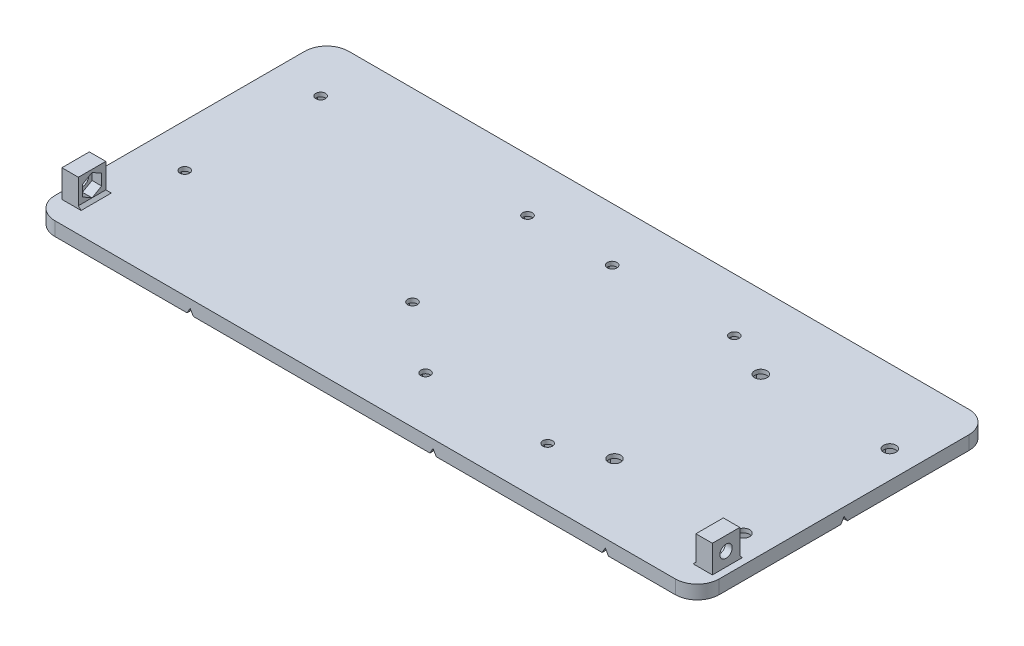
SolidWorks part; units mm, degrees
ref_plane "Front Plane" through (0, 0, 0) normal (0, 0, 1) x (1, 0, 0)
ref_plane "Top Plane" through (0, 0, 0) normal (0, 1, 0) x (1, 0, 0)
ref_plane "Right Plane" through (0, 0, 0) normal (1, 0, 0) x (0, 0, -1)
sketch "Sketch3" plane through (0, 0, 0) normal (0, 1, 0) x (1, 0, 0)
  line L0 (-65.75, 19.405) -> (13.75, 19.405) construction
  line L1 (-67.5, 17.655) -> (-67.5, 16.655) construction
  line L2 (20.25, 16.655) -> (-82.25, 16.655) construction
  line L3 (82.25, -3.845) -> (32.25, -3.845) construction
  line L4 (20.25, 16.655) -> (20.25, 69.655) construction
  line L5 (20.25, 69.655) -> (-82.25, 69.655) construction
  line L6 (-82.25, 16.655) -> (-82.25, 69.655) construction
  line L7 (-69.25, 19.405) -> (-82.25, 19.405) construction
  line L8 (17.25, 19.405) -> (20.25, 19.405) construction
  line L9 (15.5, 17.655) -> (15.5, 16.655) construction
  line L10 (-82.25, 69.655) -> (-82.25, 75.655) construction
  line L11 (-82.25, 69.655) -> (-88.25, 69.655) construction
  line L12 (-79.25, 6.345) -> (-79.25, 7.345) construction
  line L13 (-81.25, 7.345) -> (-15.25, 7.345) construction
  line L14 (-81.25, 7.345) -> (-81.25, -68.655) construction
  line L15 (-81.25, -68.655) -> (-15.25, -68.655) construction
  line L16 (-15.25, 7.345) -> (-15.25, -68.655) construction
  line L17 (-80.25, 5.345) -> (-81.25, 5.345) construction
  line L18 (-17.25, 6.345) -> (-17.25, 7.345) construction
  line L19 (-16.25, 5.345) -> (-15.25, 5.345) construction
  line L20 (-16.25, -66.655) -> (-15.25, -66.655) construction
  line L21 (-17.25, -67.655) -> (-17.25, -68.655) construction
  line L22 (-80.25, -66.655) -> (-81.25, -66.655) construction
  line L23 (-79.25, -67.655) -> (-79.25, -68.655) construction
  line L24 (82.25, -3.845) -> (82.25, 69.655) construction
  line L25 (82.25, 69.655) -> (32.25, 69.655) construction
  line L26 (32.25, -3.845) -> (32.25, 69.655) construction
  line L27 (26.74, -7.845) -> (82.25, -7.845) construction
  line L28 (26.74, -7.845) -> (26.74, -69.655) construction
  line L29 (26.74, -69.655) -> (82.25, -69.655) construction
  line L30 (82.25, -7.845) -> (82.25, -69.655) construction
  line L31 (-88.25, 75.655) -> (88.25, 75.655) construction
  line L32 (-88.25, 75.655) -> (-88.25, -75.655) construction
  line L33 (-88.25, -75.655) -> (88.25, -75.655) construction
  line L34 (88.25, 75.655) -> (88.25, -75.655) construction
  line L35 (82.25, 69.655) -> (82.25, 75.655) construction
  line L36 (82.25, 69.655) -> (88.25, 69.655) construction
  line L37 (82.25, -69.655) -> (88.25, -69.655) construction
  line L38 (82.25, -69.655) -> (82.25, -75.655) construction
  line L39 (35, 68.655) -> (35, 69.655) construction
  line L40 (33.25, 66.905) -> (32.25, 66.905) construction
  line L41 (79.5, 68.655) -> (79.5, 69.655) construction
  line L42 (81.25, 66.905) -> (82.25, 66.905) construction
  line L43 (81.25, -1.095) -> (82.25, -1.095) construction
  line L44 (79.5, -2.845) -> (79.5, -3.845) construction
  line L45 (35, -2.845) -> (35, -3.845) construction
  line L46 (33.25, -1.095) -> (32.25, -1.095) construction
  line L47 (30.99, -9.845) -> (30.99, -7.845) construction
  line L48 (28.74, -12.095) -> (26.74, -12.095) construction
  line L49 (20.25, 69.655) -> (32.25, 69.655) construction
  line L50 (-66.03, -35.735) -> (-66.03, -25.575) construction
  line L51 (-30.47, -35.735) -> (-30.47, -25.575) construction
  line L52 (-66.03, -30.655) -> (-30.47, -30.655) construction
  line L53 (-76.19, -40.815) -> (-76.19, -20.495) construction
  line L54 (-76.19, -30.655) -> (-20.31, -30.655) construction
  line L55 (-20.31, -30.655) -> (-20.31, -20.495) construction
  line L56 (-70.75, -14) -> (8.75, -14) construction
  line L57 (88.25, -75.655) -> (153.76, -75.655) construction
  line L58 (153.76, -75.655) -> (153.76, 75.655) construction
  line L59 (153.76, 75.655) -> (88.25, 75.655) construction
  line L60 (153.76, 0) -> (-88.25, 0) construction
  line L61 (96.75, -26.655) -> (96.75, 26.655) construction
  line L62 (35.25, 34) -> (35.25, -34) construction
  line L63 (-88.25, 53.5) -> (153.76, 53.5)
  line L64 (153.76, 53.5) -> (153.76, -53.5)
  line L65 (153.76, -53.5) -> (-88.25, -53.5)
  line L66 (-88.25, -53.5) -> (-88.25, 53.5)
  line L67 (4.2468, -45.5) -> (4.2468, 45.5) construction
  line L68 (-72.5, -14) -> (-72.5, 34.26) construction
  line L69 (10.5, -14) -> (10.5, 34.26) construction
  line L70 (10.5, 34.26) -> (4.15, 34.26) construction
  circle A0 centre (-67.5, 19.405) radius 1.75 construction
  circle A1 centre (15.5, 19.405) radius 1.75 construction
  circle A2 centre (-79.25, 5.345) radius 1 construction
  circle A3 centre (-17.25, 5.345) radius 1 construction
  circle A4 centre (-79.25, -66.655) radius 1 construction
  circle A5 centre (-17.25, -66.655) radius 1 construction
  circle A6 centre (35, 66.905) radius 1.75 construction
  circle A7 centre (79.5, 66.905) radius 1.75 construction
  circle A8 centre (35, -1.095) radius 1.75 construction
  circle A9 centre (79.5, -1.095) radius 1.75 construction
  circle A10 centre (30.99, -65.405) radius 2.25 construction
  circle A11 centre (30.99, -12.095) radius 2.25 construction
  circle A12 centre (78, -12.095) radius 2.25 construction
  circle A13 centre (78, -65.405) radius 2.25 construction
  circle A14 centre (-66.03, -25.575) radius 1.75 construction
  circle A15 centre (-30.47, -25.575) radius 1.75 construction
  circle A16 centre (-66.03, -35.735) radius 1.75 construction
  circle A17 centre (-30.47, -35.735) radius 1.75 construction
  circle A18 centre (-76.19, -20.495) radius 1.75 construction
  circle A19 centre (-20.31, -20.495) radius 1.75 construction
  circle A20 centre (-20.31, -40.815) radius 1.75 construction
  circle A21 centre (-76.19, -40.815) radius 1.75 construction
  circle A22 centre (-72.5, -14) radius 1.75
  circle A23 centre (10.5, -14) radius 1.75
  circle A24 centre (96.75, -26.655) radius 2.25
  circle A25 centre (96.75, 26.655) radius 2.25
  circle A26 centre (143.76, 26.655) radius 2.25
  circle A27 centre (143.76, -26.655) radius 2.25
  circle A28 centre (35.25, 34) radius 1.75
  circle A29 centre (79.75, 34) radius 1.75
  circle A30 centre (35.25, -34) radius 1.75
  circle A31 centre (79.75, -34) radius 1.75
  circle A33 centre (-71.23, 34.26) radius 1.75
  circle A34 centre (4.15, 34.26) radius 1.75
  point P60 (0, 75.655)
  point P62 (-88.25, 0)
  point P111 (-81.25, -30.655)
  point P112 (-66.03, -30.655)
  point P115 (-48.25, 7.345)
  point P116 (-48.25, -30.655)
  point P125 (-76.19, -30.655)
  point P129 (-48.25, -30.655)
  point P145 (35.25, 0)
  point P146 (96.75, 0)
  point P149 (153.76, 0)
  point P164 (4.2468, 0)
  dimension "D1" = 3.5
  dimension "D8" = 2
  dimension "D22" = 4.5
  dimension "D24" = 3.5
  dimension "D2" = 79.5
  dimension "D3" = 53
  dimension "D4" = 13
  dimension "D5" = 1
  dimension "D6" = 66
  dimension "D7" = 76
  dimension "D9" = 1
  dimension "D10" = 73.5
  dimension "D11" = 61.81
  dimension "D12" = 55.51
  dimension "D13" = 6
  dimension "D14" = 4
  dimension "D15" = 12
  dimension "D16" = 7
  dimension "D17" = 3
  dimension "D18" = 50
  dimension "D19" = 7
  dimension "D20" = 53.31
  dimension "D21" = 47.01
  dimension "D23" = 2
  dimension "D25" = 35.56
  dimension "D26" = 10.16
  dimension "D27" = 20.32
  dimension "D28" = 55.88
  dimension "D29" = 5
  dimension "D30" = 14
  dimension "D31" = 47.01
  dimension "D32" = 53.31
  dimension "D33" = 44.5
  dimension "D34" = 68
  dimension "D35" = 15
  dimension "D36" = 17
  dimension "D37" = 10
  dimension "D38" = 8
  dimension "D39" = 91
  dimension "D40" = 48.26
  dimension "D41" = 1.27
  dimension "D42" = 6.35
extrude "Boss-Extrude3" add sketch "Sketch3" along normal blind 5
sketch "Sketch4" plane through (0, 0, 0) normal (0, -1, 0) x (1, 0, 0)
  line L1 (96.75, 30.6965) -> (93.25, 28.6757)
  line L2 (93.25, 28.6757) -> (93.25, 24.6343)
  line L3 (93.25, 24.6343) -> (96.75, 22.6135)
  line L4 (96.75, 22.6135) -> (100.25, 24.6343)
  line L5 (100.25, 24.6343) -> (100.25, 28.6757)
  line L6 (100.25, 28.6757) -> (96.75, 30.6965)
  line L7 (143.76, 30.6965) -> (140.26, 28.6757)
  line L8 (140.26, 28.6757) -> (140.26, 24.6343)
  line L9 (140.26, 24.6343) -> (143.76, 22.6135)
  line L10 (143.76, 22.6135) -> (147.26, 24.6343)
  line L11 (147.26, 24.6343) -> (147.26, 28.6757)
  line L12 (147.26, 28.6757) -> (143.76, 30.6965)
  line L13 (96.75, -22.6135) -> (93.25, -24.6343)
  line L14 (93.25, -24.6343) -> (93.25, -28.6757)
  line L15 (93.25, -28.6757) -> (96.75, -30.6965)
  line L16 (96.75, -30.6965) -> (100.25, -28.6757)
  line L17 (100.25, -28.6757) -> (100.25, -24.6343)
  line L18 (100.25, -24.6343) -> (96.75, -22.6135)
  line L19 (143.76, -30.6965) -> (147.26, -28.6757)
  line L20 (147.26, -28.6757) -> (147.26, -24.6343)
  line L21 (147.26, -24.6343) -> (143.76, -22.6135)
  line L22 (143.76, -22.6135) -> (140.26, -24.6343)
  line L23 (140.26, -24.6343) -> (140.26, -28.6757)
  line L24 (140.26, -28.6757) -> (143.76, -30.6965)
  line L49 (-72.5, 17.1177) -> (-75.2, 15.5588)
  line L50 (-75.2, 15.5588) -> (-75.2, 12.4412)
  line L51 (-75.2, 12.4412) -> (-72.5, 10.8823)
  line L52 (-72.5, 10.8823) -> (-69.8, 12.4412)
  line L53 (-69.8, 12.4412) -> (-69.8, 15.5588)
  line L54 (-69.8, 15.5588) -> (-72.5, 17.1177)
  line L55 (10.5, 17.1177) -> (7.8, 15.5588)
  line L56 (7.8, 15.5588) -> (7.8, 12.4412)
  line L57 (7.8, 12.4412) -> (10.5, 10.8823)
  line L58 (10.5, 10.8823) -> (13.2, 12.4412)
  line L59 (13.2, 12.4412) -> (13.2, 15.5588)
  line L60 (13.2, 15.5588) -> (10.5, 17.1177)
  line L61 (35.25, 37.1177) -> (32.55, 35.5588)
  line L62 (32.55, 35.5588) -> (32.55, 32.4412)
  line L63 (32.55, 32.4412) -> (35.25, 30.8823)
  line L64 (35.25, 30.8823) -> (37.95, 32.4412)
  line L65 (37.95, 32.4412) -> (37.95, 35.5588)
  line L66 (37.95, 35.5588) -> (35.25, 37.1177)
  line L67 (79.75, 37.1177) -> (77.05, 35.5588)
  line L68 (77.05, 35.5588) -> (77.05, 32.4412)
  line L69 (77.05, 32.4412) -> (79.75, 30.8823)
  line L70 (79.75, 30.8823) -> (82.45, 32.4412)
  line L71 (82.45, 32.4412) -> (82.45, 35.5588)
  line L72 (82.45, 35.5588) -> (79.75, 37.1177)
  line L73 (79.75, -30.8823) -> (77.05, -32.4412)
  line L74 (77.05, -32.4412) -> (77.05, -35.5588)
  line L75 (77.05, -35.5588) -> (79.75, -37.1177)
  line L76 (79.75, -37.1177) -> (82.45, -35.5588)
  line L77 (82.45, -35.5588) -> (82.45, -32.4412)
  line L78 (82.45, -32.4412) -> (79.75, -30.8823)
  line L79 (35.25, -30.8823) -> (32.55, -32.4412)
  line L80 (32.55, -32.4412) -> (32.55, -35.5588)
  line L81 (32.55, -35.5588) -> (35.25, -37.1177)
  line L82 (35.25, -37.1177) -> (37.95, -35.5588)
  line L83 (37.95, -35.5588) -> (37.95, -32.4412)
  line L84 (37.95, -32.4412) -> (35.25, -30.8823)
  line L86 (-71.23, -31.1423) -> (-73.93, -32.7012)
  line L87 (-73.93, -32.7012) -> (-73.93, -35.8188)
  line L88 (-73.93, -35.8188) -> (-71.23, -37.3777)
  line L89 (-71.23, -37.3777) -> (-68.53, -35.8188)
  line L90 (-68.53, -35.8188) -> (-68.53, -32.7012)
  line L91 (-68.53, -32.7012) -> (-71.23, -31.1423)
  line L93 (4.15, -31.1423) -> (1.45, -32.7012)
  line L94 (1.45, -32.7012) -> (1.45, -35.8188)
  line L95 (1.45, -35.8188) -> (4.15, -37.3777)
  line L96 (4.15, -37.3777) -> (6.85, -35.8188)
  line L97 (6.85, -35.8188) -> (6.85, -32.7012)
  line L98 (6.85, -32.7012) -> (4.15, -31.1423)
  circle A0 centre (96.75, 26.655) radius 3.5 construction
  circle A1 centre (143.76, 26.655) radius 3.5 construction
  circle A2 centre (96.75, -26.655) radius 3.5 construction
  circle A3 centre (143.76, -26.655) radius 3.5 construction
  circle A8 centre (-72.5, 14) radius 2.7 construction
  circle A9 centre (10.5, 14) radius 2.7 construction
  circle A10 centre (35.25, 34) radius 2.7 construction
  circle A11 centre (79.75, 34) radius 2.7 construction
  circle A12 centre (79.75, -34) radius 2.7 construction
  circle A13 centre (35.25, -34) radius 2.7 construction
  circle A14 centre (-71.23, -34.26) radius 2.7 construction
  circle A15 centre (4.15, -34.26) radius 2.7 construction
  dimension "D1" = 7
  dimension "D2" = 5.4
extrude "Cut-Extrude1" cut sketch "Sketch4" against normal blind 3.5
ref_plane "Plane1" through (0, 0, 51) normal (0, 0, 1) x (1, 0, 0)
sketch "Sketch7" plane through (0, 0, 51) normal (0, 0, 1) x (1, 0, 0)
  line L1 (-5, 5) -> (5, 5) construction
  line L2 (-5, 5) -> (-5, 15) construction
  line L3 (-5, 15) -> (5, 15) construction
  line L4 (5, 5) -> (5, 15) construction
  line L5 (-88.25, 5) -> (153.76, 5) construction
  line L6 (53, 5) -> (63, 5)
  line L7 (53, 5) -> (53, 15)
  line L8 (53, 15) -> (63, 15)
  line L9 (63, 5) -> (63, 15)
  circle A0 centre (0, 10) radius 2.25 construction
  circle A1 centre (58, 10) radius 2.25
  point P6 (0, 5)
  point P10 (-5, 10)
  point P12 (0, 15)
  point P15 (58, 15)
  point P16 (53, 10)
  dimension "D2" = 4.5
  dimension "D3" = 4.5
  dimension "D1" = 10
  dimension "D4" = 10
  dimension "D5" = 58
extrude "Boss-Extrude4" add sketch "Sketch7" against normal blind 6
sketch "Sketch8" plane through (0, 0, 45) normal (0, 0, -1) x (-1, 0, 0)
  line L1 (-58, 14.0126) -> (-61.475, 12.0063)
  line L2 (-61.475, 12.0063) -> (-61.475, 7.9937)
  line L3 (-61.475, 7.9937) -> (-58, 5.9874)
  line L4 (-58, 5.9874) -> (-54.525, 7.9937)
  line L5 (-54.525, 7.9937) -> (-54.525, 12.0063)
  line L6 (-54.525, 12.0063) -> (-58, 14.0126)
  circle A0 centre (-58, 10) radius 3.475 construction
  dimension "D1" = 6.95
extrude "Cut-Extrude2" cut sketch "Sketch8" against normal blind 3.5
ref_plane "Plane2" through (0, 0, 0) normal (0, 0, 1) x (1, 0, 0)
mirror "Mirror1" about plane through (0, 0, 0) normal (0, 0, 1) of "Cut-Extrude2", "Boss-Extrude4"
fillet "Fillet1" radius 8 4 edges at (153.76, 2.5, -53.5) (153.76, 2.5, 53.5) (-88.25, 2.5, 53.5) (-88.25, 2.5, -53.5)
sketch "Sketch9" plane through (0, 5, 0) normal (0, 1, 0) x (1, 0, 0)
  line L1 (38.9746, -70.9676) -> (68.2957, -70.9676)
  line L2 (38.9746, -70.9676) -> (38.9746, 58.223)
  line L3 (38.9746, 58.223) -> (68.2957, 58.223)
  line L4 (68.2957, -70.9676) -> (68.2957, 58.223)
extrude "Cut-Extrude3" cut sketch "Sketch9" along normal up to next
ref_plane "Plane3" through (151.26, 0, 0) normal (1, 0, 0) x (0, 0, -1)
sketch "Sketch10" plane through (151.26, 0, 0) normal (1, 0, 0) x (0, 0, -1)
  line L0 (-45.5, 5) -> (45.5, 5) construction
  line L1 (-35.5, 5) -> (-45.5, 5)
  line L2 (-35.5, 5) -> (-35.5, 15)
  line L3 (-35.5, 15) -> (-45.5, 15)
  line L4 (-45.5, 5) -> (-45.5, 15)
  line L5 (-45.5, 5) -> (-45.5, 0) construction
  circle A0 centre (-40.5, 10) radius 2.25
  point P10 (-40.5, 15)
  point P11 (-45.5, 10)
  dimension "D2" = 4.5
  dimension "D1" = 10
extrude "Boss-Extrude5" add sketch "Sketch10" against normal blind 6
sketch "Sketch11" plane through (145.26, 0, 0) normal (-1, 0, 0) x (0, 0, 1)
  line L1 (40.5, 14.0126) -> (37.025, 12.0063)
  line L2 (37.025, 12.0063) -> (37.025, 7.9937)
  line L3 (37.025, 7.9937) -> (40.5, 5.9874)
  line L4 (40.5, 5.9874) -> (43.975, 7.9937)
  line L5 (43.975, 7.9937) -> (43.975, 12.0063)
  line L6 (43.975, 12.0063) -> (40.5, 14.0126)
  circle A0 centre (40.5, 10) radius 3.475 construction
  dimension "D1" = 6.95
extrude "Cut-Extrude4" cut sketch "Sketch11" against normal blind 3.5
ref_plane "Plane4" through (32.755, 0, 0) normal (1, 0, 0) x (0, 0, -1)
mirror "Mirror2" about plane through (32.755, 0, 0) normal (1, 0, 0) of "Cut-Extrude4", "Boss-Extrude5"
sketch "Sketch12" plane through (0, 0, 0) normal (0, -1, 0) x (1, 0, 0)
  line L0 (-80.25, 53.5) -> (145.76, 53.5) construction
  line L1 (-33.5, 53.5) -> (-28.5, 53.5)
  line L2 (-33.5, 53.5) -> (-33.5, -53.5)
  line L3 (-33.5, -53.5) -> (-28.5, -53.5)
  line L4 (-28.5, 53.5) -> (-28.5, -53.5)
  line L5 (145.76, -53.5) -> (-80.25, -53.5) construction
  line L6 (7.8, 14) -> (-69.8, 14) construction
  line L7 (117.755, -53.5) -> (122.755, -53.5)
  line L8 (117.755, -53.5) -> (117.755, 53.5)
  line L9 (117.755, 53.5) -> (122.755, 53.5)
  line L10 (122.755, -53.5) -> (122.755, 53.5)
  line L11 (55, 53.5) -> (60, 53.5)
  line L12 (55, 53.5) -> (55, -53.5)
  line L13 (55, -53.5) -> (60, -53.5)
  line L14 (60, 53.5) -> (60, -53.5)
  line L15 (7.8, 15.5588) -> (7.8, 12.4412) construction
  line L16 (-69.8, 12.4412) -> (-69.8, 15.5588) construction
  line L17 (37.95, 34) -> (77.05, 34) construction
  line L18 (37.95, 32.4412) -> (37.95, 35.5588) construction
  line L19 (77.05, 35.5588) -> (77.05, 32.4412) construction
  line L20 (100.25, 26.655) -> (140.26, 26.655) construction
  line L21 (100.25, 24.6343) -> (100.25, 28.6757) construction
  line L22 (140.26, 28.6757) -> (140.26, 24.6343) construction
  point P34 (120.255, 53.5)
  point P35 (120.255, 26.655)
  point P36 (57.5, 34)
  point P37 (57.5, 53.5)
  point P38 (-31, 14)
  point P39 (-31, 53.5)
  dimension "D1" = 5
sketch "Sketch13" plane through (0, 0, 53.5) normal (0, 0, 1) x (1, 0, 0)
  line L0 (-32.1547, 0) -> (-31, 2)
  line L1 (-80.25, 0) -> (145.76, 0) construction
  line L2 (-31, 2) -> (-29.8453, 0)
  line L3 (-29.8453, 0) -> (-32.1547, 0)
  line L4 (-33.5, 0) -> (-28.5, 0) construction
  line L5 (-28.5, 0) -> (55, 0) construction
  line L6 (60, 0) -> (117.755, 0) construction
  line L7 (13.25, 0) -> (13.25, 30.3991) construction
  line L8 (56.3453, 0) -> (58.6547, 0)
  line L9 (57.5, 2) -> (56.3453, 0)
  line L10 (58.6547, 0) -> (57.5, 2)
  line L11 (88.8775, 0) -> (88.8775, 17.3926) construction
  line L12 (119.1003, 0) -> (120.255, 2)
  line L13 (120.255, 2) -> (121.4097, 0)
  line L14 (121.4097, 0) -> (119.1003, 0)
  point P7 (-31, 0)
  dimension "D1" = 2
extrude "Cut-Extrude5" cut sketch "Sketch13" against normal through all both and the other way through all
sketch "Sketch14" plane through (-88.25, 0, 0) normal (-1, 0, 0) x (0, 0, 1)
  line L0 (-1.1547, 0) -> (1.1547, 0)
  line L1 (-45.5, 0) -> (45.5, 0) construction
  line L2 (1.1547, 0) -> (0, 2)
  line L3 (0, 2) -> (-1.1547, 0)
  point P5 (0, 0)
  dimension "D1" = 2
extrude "Cut-Extrude6" cut sketch "Sketch14" against normal through all both
chamfer "Chamfer1" distance 1 angle 45 4 edges at (145.26, 5, 40.5) (-79.75, 5, 40.5) (148.26, 5, 35.5) (-82.75, 5, 35.5)
